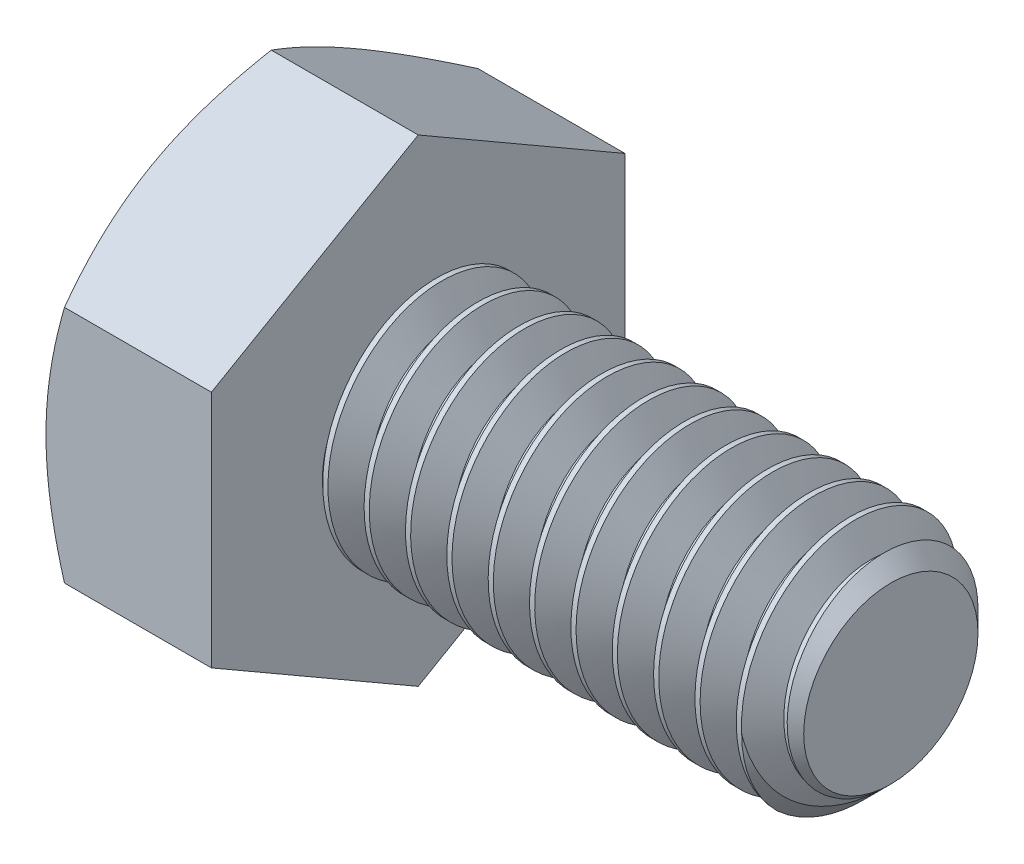
SolidWorks part; units mm, degrees
material "AISI 316 Stainless Steel Sheet (SS)"
ref_plane "Front Plane" through (0, 0, 0) normal (0, 0, 1) x (1, 0, 0)
ref_plane "Top Plane" through (0, 0, 0) normal (0, 1, 0) x (1, 0, 0)
ref_plane "Right Plane" through (0, 0, 0) normal (1, 0, 0) x (0, 0, -1)
sketch "Sketch1" plane through (0, 0, 0) normal (0, 0, 1) x (1, 0, 0)
  line L0 (-5.4, 0) -> (5.4, 0) construction
  line L1 (-2.6, 3.5) -> (-2.6, -3.5) construction
  line L2 (-5.4, 3.5) -> (-5.4, -3.5) construction
  line L3 (5.4, 2) -> (5.4, -2) construction
  point P8 (2.95, -2)
  dimension "Thread Dia" = 4
  dimension "Hex" = 7
  dimension "Head Ht" = 2.8
  dimension "Length" = 8
  dimension "D1" = 2.45
ref_plane "Plane2" through (5.4, 0, 0) normal (1, 0, 0) x (0, 0, -1)
sketch "Sketch2" plane through (5.4, 0, 0) normal (1, 0, 0) x (0, 0, -1)
  circle A0 centre (0, 0) radius 2
extrude "Boss-Extrude1" add sketch "Sketch2" against normal up to vertex (8 mm away) up to point (-2.6, -3.5, 0)
sketch "Sketch4" plane through (5.4, 0, 0) normal (1, 0, 0) x (0, 0, -1)
  circle A1 centre (0, 0) radius 2
  circle A2 centre (0, 0) radius 2
  dimension "D1" = 0
curve "Helix/Spiral1" pitch 0.7 height 8.7 turns 12.4286 parameters "Pitch"=0.7
chamfer "Chamfer1" distance 0.525 angle 45 1 edges at (5.4, 0, -2)
sketch "Sketch5" plane through (0, 0, 0) normal (0, 0, 1) x (1, 0, 0)
  line L0 (5.4, 2) -> (5.6625, 1.5453)
  line L1 (5.6625, 1.5453) -> (5.75, 1.5453)
  line L2 (5.75, 1.5453) -> (6.0125, 2)
  line L3 (5.4, 2) -> (6.0125, 2)
  line L4 (5.7063, 1.5453) -> (5.7063, 2) construction
  line L5 (5.5313, 1.7727) -> (5.8813, 1.7727) construction
  line L6 (5.4, -2) -> (5.4, 2) construction
  dimension "D1" = 60
  dimension "D2" = 0.0875
  dimension "D3" = 0.35
sweep "Cut-Sweep1" cut profiles "Sketch5" path "Helix/Spiral1" align with end faces yes
sketch "Sketch3" plane through (-2.6, 0, 0) normal (-1, 0, 0) x (0, 0, 1)
  line L0 (0, 3.5) -> (0, -3.5) construction
  line L1 (-3.5, -2.0207) -> (0, -4.0415)
  line L2 (0, -4.0415) -> (3.5, -2.0207)
  line L3 (3.5, -2.0207) -> (3.5, 2.0207)
  line L4 (3.5, 2.0207) -> (0, 4.0415)
  line L5 (0, 4.0415) -> (-3.5, 2.0207)
  line L6 (-3.5, 2.0207) -> (-3.5, -2.0207)
  circle A0 centre (0, 0) radius 3.5 construction
extrude "Boss-Extrude2" add sketch "Sketch3" along normal up to vertex (2.8 mm away) up to point (-5.4, -3.5, 0)
sketch "Sketch6" plane through (-5.4, 0, 0) normal (-1, 0, 0) x (0, 0, 1)
  circle A0 centre (0, 0) radius 3.5 construction
  circle A1 centre (0, 0) radius 3.5
extrude "Cut-Extrude1" cut sketch "Sketch6" against normal through all draft 60 flip side to cut
sketch "Sketch7" plane through (-5.4, 0, 0) normal (-1, 0, 0) x (0, 0, 1)
  line L0 (0, 0) -> (0, 3.5) construction
  line L2 (0, 3.5) -> (0, -3.5) construction
  line L3 (-3.0311, 1.75) -> (3.0311, 1.75) construction
  circle A1 centre (0, 0) radius 3.5 construction
  text T0 "10.9\r\n" font "Arial" height in points 28
  point P8 (0, 1.75)
equation "\"D2@Sketch5\" = \"Pitch@Helix/Spiral1\"*.125"
equation "\"D3@Sketch5\" = \"Pitch@Helix/Spiral1\"*.50"
equation "\"D3@Helix/Spiral1\" = \"Length@Sketch1\"+\"Pitch@Helix/Spiral1\""
equation "\"D1@Chamfer1\" = \"Pitch@Helix/Spiral1\"*.750"
equation "\"D1@Sketch1\" = \"Pitch@Helix/Spiral1\"*3.50"
